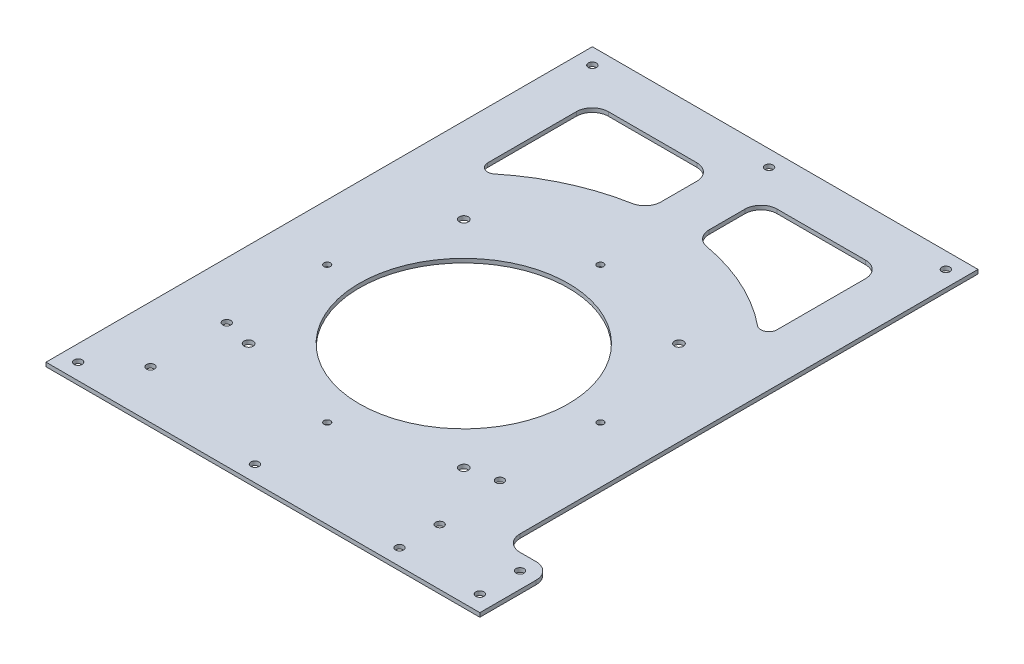
SolidWorks part; units mm, degrees
material "6061-T6 (SS)"
ref_plane "Front Plane" through (0, 0, 0) normal (0, 0, 1) x (1, 0, 0)
ref_plane "Top Plane" through (0, 0, 0) normal (0, 1, 0) x (1, 0, 0)
ref_plane "Right Plane" through (0, 0, 0) normal (1, 0, 0) x (0, 0, -1)
sketch "Sketch1" plane through (0, 0, 0) normal (0, 1, 0) x (1, 0, 0)
  line L0 (0, 177.8) -> (0, -177.8) construction
  line L1 (152.4, -177.8) -> (-152.4, -177.8)
  line L2 (152.4, -177.8) -> (152.4, 254) construction
  line L3 (152.4, 254) -> (-152.4, 254)
  line L4 (-152.4, -177.8) -> (-152.4, 254)
  line L5 (152.4, -177.8) -> (-152.4, 254) construction
  line L6 (152.4, 254) -> (-152.4, -177.8) construction
  line L7 (152.4, -120.65) -> (152.4, 254)
  line L8 (152.4, -120.65) -> (190.5, -120.65)
  line L10 (152.4, -177.8) -> (190.5, -177.8)
  line L11 (190.5, -120.65) -> (190.5, -177.8)
  point P0 (0, 38.1)
  point P12 (0, 0)
  dimension "D1" = 355.6
  dimension "D2" = 304.8
  dimension "D3" = 431.8
  dimension "D4" = 57.15
  dimension "D5" = 38.1
base flange "Base-Flange1" sketch "Sketch1" thickness 3.175 reverse thickness direction no parameters "D1"=0.7366
sketch "Sketch2" plane through (0, 0, 0) normal (0, 1, 0) x (1, 0, 0)
  line L0 (-139.7, 254) -> (-139.7, -177.8) construction
  line L1 (152.4, 254) -> (-152.4, 254) construction
  line L2 (-152.4, -177.8) -> (190.5, -177.8) construction
  line L3 (-152.4, 254) -> (-152.4, -177.8) construction
  line L4 (-152.4, -177.8) -> (190.5, -177.8) construction
  line L5 (152.4, -120.65) -> (152.4, 254) construction
  line L6 (-152.4, 38.1) -> (152.4, 38.1) construction
  line L8 (0, 254) -> (0, -177.8) construction
  circle A0 centre (-107.95, 0) radius 2.5781 construction
  circle A1 centre (0, 107.95) radius 2.5781 construction
  circle A2 centre (107.95, 0) radius 2.5781 construction
  circle A3 centre (85.034, 85.034) radius 3.5687 construction
  circle A4 centre (85.034, -85.034) radius 3.5687 construction
  circle A5 centre (-107.95, 0) radius 2.5781
  circle A6 centre (0, 107.95) radius 2.5781
  circle A7 centre (107.95, 0) radius 2.5781
  circle A8 centre (85.034, 85.034) radius 3.5687
  circle A9 centre (85.034, -85.034) radius 3.5687
  circle A10 centre (0, -107.95) radius 2.5781 construction
  circle A11 centre (-85.034, -85.034) radius 3.5687 construction
  circle A12 centre (-85.034, 85.034) radius 3.5687 construction
  circle A13 centre (0, -107.95) radius 2.5781
  circle A14 centre (-85.034, -85.034) radius 3.5687
  circle A15 centre (-85.034, 85.034) radius 3.5687
  circle A16 centre (0, 241.3) radius 3.175
  circle A17 centre (-139.7, 241.3) radius 3.175
  circle A18 centre (0, -165.1) radius 3.175
  circle A19 centre (177.8, -165.1) radius 3.175 construction
  circle A20 centre (-139.7, -165.1) radius 3.175
  circle A22 centre (177.8, -133.35) radius 3.175 construction
  circle A24 centre (114.3, -165.1) radius 3.175 construction
  circle A25 centre (139.7, 241.3) radius 3.175
  circle A26 centre (177.8, -165.1) radius 3.175
  circle A27 centre (177.8, -133.35) radius 3.175
  circle A29 centre (114.3, -165.1) radius 3.175
  circle A30 centre (107.95, -79.375) radius 3.175 construction
  circle A31 centre (114.3, -133.35) radius 3.175 construction
  circle A32 centre (-107.95, -79.375) radius 3.175 construction
  circle A33 centre (-107.95, -139.7) radius 3.175 construction
  circle A34 centre (107.95, -79.375) radius 3.175
  circle A35 centre (114.3, -133.35) radius 3.175
  circle A36 centre (-107.95, -79.375) radius 3.175
  circle A37 centre (-107.95, -139.7) radius 3.175
  dimension "D4" = 6.35
  dimension "D2" = 12.7
  dimension "D3" = 12.7
extrude "Cut-Extrude1" cut sketch "Sketch2" against normal through all normal cut yes
fillet "Fillet1" radius 12.7 2 edges at (190.5, -1.5875, 120.65) (152.4, -1.5875, 120.65)
sketch "Sketch3" plane through (0, 0, 0) normal (0, 1, 0) x (1, 0, 0)
  line L0 (114.3, 203.2) -> (114.3, 133.1987)
  line L1 (152.4, -107.95) -> (152.4, 254) construction
  line L2 (101.6, 215.9) -> (31.75, 215.9)
  line L3 (19.05, 203.2) -> (19.05, 174.9422)
  line L4 (0, 241.3) -> (0, 0) construction
  line L5 (152.4, 254) -> (-152.4, 254) construction
  line L6 (-101.6, 215.9) -> (-31.75, 215.9)
  line L7 (-19.05, 203.2) -> (-19.05, 174.9422)
  line L8 (-114.3, 203.2) -> (-114.3, 133.1987)
  circle A0 centre (0, 0) radius 82.55
  circle A1 centre (0, 0) radius 152.4 construction
  arc A2 (103.9519, 128.2654) -> (29.4821, 162.4463) centre (0, 0) ccw
  arc A3 (29.4821, 162.4463) -> (19.05, 174.9422) centre (31.75, 174.9422) cw
  arc A4 (114.3, 203.2) -> (101.6, 215.9) centre (101.6, 203.2) ccw
  arc A5 (31.75, 215.9) -> (19.05, 203.2) centre (31.75, 203.2) ccw
  arc A6 (114.3, 133.1987) -> (103.9519, 128.2654) centre (107.95, 133.1987) cw
  arc A7 (-31.75, 215.9) -> (-19.05, 203.2) centre (-31.75, 203.2) cw
  arc A8 (-29.4821, 162.4463) -> (-19.05, 174.9422) centre (-31.75, 174.9422) ccw
  arc A9 (-103.9519, 128.2654) -> (-29.4821, 162.4463) centre (0, 0) cw
  arc A10 (-114.3, 133.1987) -> (-103.9519, 128.2654) centre (-107.95, 133.1987) ccw
  arc A11 (-114.3, 203.2) -> (-101.6, 215.9) centre (-101.6, 203.2) cw
  dimension "D1" = 165.1
  dimension "D2" = 304.8
  dimension "D5" = 12.7
  dimension "D7" = 12.7
  dimension "D8" = 6.35
  dimension "D3" = 38.1
  dimension "D4" = 38.1
  dimension "D6" = 38.1
extrude "Cut-Extrude2" cut sketch "Sketch3" against normal through all normal cut yes
sketch "Bend-Lines1" [suppressed] plane through (0, 0, 0) normal (0, 1, 0) x (1, 0, 0)
sketch "Bounding-Box1" [suppressed] plane through (0, 0, 0) normal (0, 1, 0) x (1, 0, 0)
sheet metal parameters "Sheet-Metal1" thickness 3.175 parameters "D1"=0.7366
flat pattern "Flat-Pattern1" [suppressed]
sketch "Bend-Lines2" plane through (0, 0, 0) normal (0, 1, 0) x (1, 0, 0)
sketch3d "Bounding-Box2" [suppressed]
  line L0 (-152.4, 247.65, 0) -> (-152.4, -158.75, 0) construction
  line L1 (190.5, 247.65, 0) -> (190.5, -158.75, 0) construction
  line L2 (-152.4, 247.65, 0) -> (190.5, 247.65, 0) construction
  line L3 (-152.4, -158.75, 0) -> (190.5, -158.75, 0) construction
sheet metal parameters "Sheet-Metal2" thickness 3.175 parameters "D1"=0.7366
flat pattern "Flat-Pattern1"
sketch "Bend-Lines2" plane through (0, 0, 0) normal (0, 1, 0) x (1, 0, 0)
sketch3d "Bounding-Box2" [suppressed]
  line L0 (-152.4, 254, 0) -> (-152.4, -177.8, 0) construction
  line L1 (190.5, 254, 0) -> (190.5, -177.8, 0) construction
  line L2 (-152.4, 254, 0) -> (190.5, 254, 0) construction
  line L3 (-152.4, -177.8, 0) -> (190.5, -177.8, 0) construction
sheet metal parameters "Sheet-Metal4" thickness 3.175 parameters "D1"=0.7366
flat pattern "Flat-Pattern1"
sketch "Bend-Lines2" plane through (0, 0, 0) normal (0, 1, 0) x (1, 0, 0)
sketch3d "Bounding-Box2" [suppressed]
  line L0 (-152.4, 254, 0) -> (-152.4, -177.8, 0) construction
  line L1 (190.5, 254, 0) -> (190.5, -177.8, 0) construction
  line L2 (-152.4, 254, 0) -> (190.5, 254, 0) construction
  line L3 (-152.4, -177.8, 0) -> (190.5, -177.8, 0) construction
